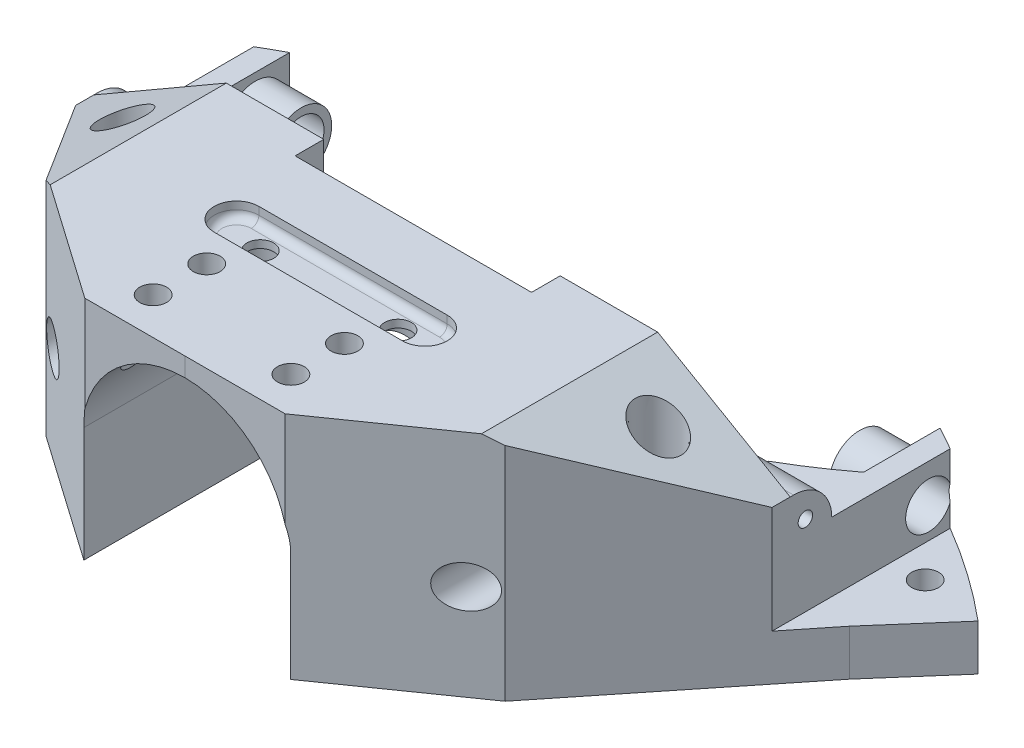
SolidWorks part; units mm, degrees
ref_plane "Front Plane" through (0, 0, 0) normal (0, 0, 1) x (1, 0, 0)
ref_plane "Top Plane" through (0, 0, 0) normal (0, 1, 0) x (1, 0, 0)
ref_plane "Right Plane" through (0, 0, 0) normal (1, 0, 0) x (0, 0, -1)
sketch "Sketch1" plane through (0, 0, 0) normal (0, 1, 0) x (1, 0, 0)
  circle A0 centre (0, 0) radius 90
extrude "Boss-Extrude1" add sketch "Sketch1" along normal blind 30
sketch "Sketch4" plane through (0, 30, 0) normal (0, 1, 0) x (1, 0, 0)
  line L0 (0, 90) -> (0, 55) construction
  line L1 (-42.5, 79.3332) -> (-42.5, 69.3332)
  line L2 (42.5, 79.3332) -> (42.5, 69.3332)
  line L3 (-42.5, 79.3332) -> (-42.5, 105.8098)
  line L4 (-42.5, 105.8098) -> (42.5, 105.8098)
  line L5 (42.5, 105.8098) -> (42.5, 79.3332)
  circle A0 centre (0, 0) radius 90 construction
  arc A1 (-42.5, 69.3332) -> (42.5, 69.3332) centre (0, 125.1761) ccw
  circle A5 centre (0, 0) radius 90 construction
  dimension "D1" = 35
  dimension "D2" = 42.5
  dimension "D3" = 42.5
  dimension "D4" = 10
  dimension "D5" = 10
extrude "Cut-Extrude2" cut sketch "Sketch4" against normal through all
sketch "Sketch9" plane through (0, 30, 0) normal (0, 1, 0) x (1, 0, 0)
  circle A0 centre (-49.7064, 70.1803) radius 1.75
  arc A1 (-42.5, 79.3332) -> (42.5, 79.3332) centre (0, 0) ccw construction
  dimension "D2" = 3.5
  dimension "D1" = 86
extrude "Cut-Extrude7" cut sketch "Sketch9" against normal through all
mirror "Mirror1" about plane through (0, 0, 0) normal (1, 0, 0) of "Cut-Extrude7"
sketch "Sketch10" plane through (0, 0, 0) normal (0, -1, 0) x (1, 0, 0)
  line L0 (57.8174, -68.9721) -> (50, -60)
  line L1 (50, -60) -> (30, -35)
  line L2 (-30, -35) -> (30, -35) construction
  line L3 (-30, -35) -> (-50, -60)
  line L4 (-50, -60) -> (-57.8174, -68.9721)
  line L5 (0, 0) -> (0, -35) construction
  line L6 (-30, -35) -> (-13.0885, -23.1584)
  line L7 (-13.0885, -23.1584) -> (0, -23.1584)
  line L8 (0, -23.1584) -> (13.0885, -23.1584)
  line L9 (13.0885, -23.1584) -> (30, -35)
  arc A0 (42.5, -79.3332) -> (-42.5, -79.3332) centre (0, 0) ccw construction
  point P14 (0, 0)
  dimension "D1" = 35
  dimension "D2" = 30
  dimension "D3" = 30
  dimension "D4" = 35
  dimension "D5" = 25
  dimension "D6" = 35
  dimension "D7" = 25
  dimension "D8" = 11.9
  dimension "D9" = 11.9
extrude "Cut-Extrude8" cut sketch "Sketch10" along direction (0, 1, 0) on the side against the normal through all and the other way through all flip side to cut
sketch "Sketch11" plane through (0, 0, -23.1584) normal (0, 0, 1) x (1, 0, 0)
  line L2 (-13.5, 15) -> (-13.5, 0)
  line L3 (-13.5, 0) -> (13.5, 0)
  line L4 (13.5, 15) -> (13.5, 0)
  arc A0 (13.5, 15) -> (-13.5, 15) centre (0, 14) ccw
  dimension "D2" = 27
  dimension "D3" = 15
  dimension "D5" = 15
sketch "Sketch13" plane through (42.5, 0, 0) normal (-1, 0, 0) x (0, 0, 1)
  line L0 (-79.3332, 0) -> (-79.3332, 30) construction
  line L1 (-69.3332, 0) -> (-79.3332, 0) construction
  circle A0 centre (-74.8332, 10) radius 4
  circle A1 centre (-74.8332, 10) radius 3
  dimension "D3" = 8
  dimension "D4" = 6
  dimension "D1" = 4.5
  dimension "D2" = 10
extrude "Boss-Extrude2" add sketch "Sketch13" along normal blind 6
sketch "Sketch14" plane through (0, 30, 0) normal (0, 1, 0) x (1, 0, 0)
  line L0 (-45.5, 77.6515) -> (-45.5, 54.375)
  line L1 (-30, 35) -> (-50, 60) construction
  line L2 (-42.5, 79.3332) -> (-42.5, 69.3332) construction
  arc A0 (-42.5, 79.3332) -> (-57.8174, 68.9721) centre (0, 0) ccw construction
  dimension "D1" = 3
extrude "Cut-Extrude11" cut sketch "Sketch14" against normal blind 24 and the other way through all flip side to cut
sketch "Sketch15" plane through (42.5, 0, 0) normal (-1, 0, 0) x (0, 0, 1)
  circle A0 centre (-74.8332, 10) radius 3
extrude "Cut-Extrude12" cut sketch "Sketch15" against normal through all
mirror "Mirror2" about plane through (0, 0, 0) normal (1, 0, 0) of "Cut-Extrude12", "Boss-Extrude2", "Cut-Extrude11"
other "Move Face1" parameters "D1"=0
ref_plane "Plane1" through (0, 0, -53) normal (0, 0, 1) x (1, 0, 0)
sketch "Sketch16" plane through (0, 0, -53) normal (0, 0, 1) x (1, 0, 0)
  line L1 (33, 19.5) -> (-33, 19.5)
  line L2 (35, 17.5) -> (35, 7.5)
  line L3 (33, 5.5) -> (-33, 5.5)
  line L4 (-35, 17.5) -> (-35, 7.5)
  line L5 (35, 19.5) -> (-35, 5.5) construction
  line L6 (35, 5.5) -> (-35, 19.5) construction
  arc A0 (-33, 19.5) -> (-35, 17.5) centre (-33, 17.5) ccw
  arc A1 (-33, 5.5) -> (-35, 7.5) centre (-33, 7.5) cw
  arc A2 (35, 7.5) -> (33, 5.5) centre (33, 7.5) cw
  arc A3 (33, 19.5) -> (35, 17.5) centre (33, 17.5) cw
  point P0 (0, 12.5)
  dimension "D3" = 2
  dimension "D1" = 5.5
  dimension "D2" = 14
  dimension "D4" = 70
  dimension "D5" = 35
extrude "Cut-Extrude13" cut sketch "Sketch16" against normal through all
sketch "Sketch17" plane through (0, 0, -53) normal (0, 0, -1) x (-1, 0, 0)
  circle A0 centre (-27, 12.5) radius 2.7228
  dimension "D1" = 12.5
  dimension "D2" = 27
extrude "Cut-Extrude14" cut sketch "Sketch17" against normal through all
mirror "Mirror3" about plane through (0, 0, 0) normal (1, 0, 0) of "Cut-Extrude14"
sketch "Sketch20" plane through (0, 30, 0) normal (0, 1, 0) x (1, 0, 0)
  line L1 (-63.9229, 90.6989) -> (72.019, 90.6989)
  line L2 (-63.9229, 90.6989) -> (-63.9229, 56.7436)
  line L3 (-63.9229, 56.7436) -> (72.019, 56.7436)
  line L4 (72.019, 90.6989) -> (72.019, 56.7436)
extrude "Cut-Extrude16" cut sketch "Sketch20" against normal blind 10
ref_plane "Plane3" through (0, 27, 0) normal (0, 1, 0) x (1, 0, 0)
sketch "Sketch21" plane through (0, 27, 0) normal (0, 1, 0) x (1, 0, 0)
  line L0 (-9, 42) -> (9, 42) construction
  line L2 (13.0885, 23.1584) -> (0, 23.1584) construction
  line L3 (0, 42) -> (0, 23.1584) construction
  circle A0 centre (-9, 42) radius 3
  circle A1 centre (9, 42) radius 3
  dimension "D4" = 6
  dimension "D5" = 6
  dimension "D1" = 18.8416
  dimension "D2" = 18
extrude "Cut-Extrude17" cut sketch "Sketch21" against normal through all
sketch "Sketch22" plane through (0, 27, 0) normal (0, -1, 0) x (1, 0, 0)
  circle A0 centre (-9, -42) radius 1.75
  circle A1 centre (9, -42) radius 1.75
  dimension "D1" = 3.5
  dimension "D2" = 3.5
extrude "Cut-Extrude18" cut sketch "Sketch22" against normal through all
sketch "Sketch23" plane through (0, 20, 0) normal (0, 1, 0) x (1, 0, 0)
  line L1 (-63.9229, 86.5905) -> (64.5271, 86.5905)
  line L2 (-63.9229, 86.5905) -> (-63.9229, 62.1813)
  line L3 (-63.9229, 62.1813) -> (64.5271, 62.1813)
  line L4 (64.5271, 86.5905) -> (64.5271, 62.1813)
extrude "Cut-Extrude19" cut sketch "Sketch23" against normal blind 5
fillet "Fillet3" radius 5 2 edges at (-38.2124, 20, -62.1813) (38.2124, 20, -62.1813)
extrude "Cut-Extrude20" cut sketch "Sketch11" against normal through all
sketch "Sketch24" plane through (0, 30, 0) normal (0, 1, 0) x (1, 0, 0)
  line L1 (-14, -71.7161) -> (14, -71.7161)
  line L2 (-14, -71.7161) -> (-14, 71.7161)
  line L3 (-14, 71.7161) -> (14, 71.7161)
  line L4 (14, -71.7161) -> (14, 71.7161)
  line L5 (-14, -71.7161) -> (14, 71.7161) construction
  line L6 (-14, 71.7161) -> (14, -71.7161) construction
  point P0 (0, 0)
  dimension "D1" = 28
pattern_linear "LPattern1" count 3 spacing 7 along (0, 0, 1) of "Cut-Extrude17", "Cut-Extrude18"
sketch "Sketch25" plane through (-45.5, 0, 0) normal (-1, 0, 0) x (0, 0, 1)
  circle A0 centre (-58.7334, 16.5025) radius 0.9425
  point P2 (-58.7334, 16.5025)
extrude "Cut-Extrude22" cut sketch "Sketch25" against normal through all
sketch "Sketch26" plane through (0, 30, 0) normal (0, 1, 0) x (1, 0, 0)
  line L0 (-12.102, 42) -> (12.5104, 42) construction
  line L1 (-12.102, 44.9197) -> (12.5104, 44.9197)
  line L2 (-12.102, 39.0803) -> (12.5104, 39.0803)
  arc A1 (-12.102, 44.9197) -> (-12.102, 39.0803) centre (-12.102, 42) ccw
  arc A2 (12.5104, 39.0803) -> (12.5104, 44.9197) centre (12.5104, 42) ccw
  circle A4 centre (-9, 28) radius 1.75 construction
  point P1 (0.2042, 42)
  point P9 (12.5104, 41.6361)
  dimension "D1" = 14
extrude "Cut-Extrude23" cut sketch "Sketch26" against normal blind 2
fillet "Fillet4" radius 1 4 edges at (15.4301, 28, -42) (0.2042, 28, -39.0803) (-15.0217, 28, -42) (0.2042, 28, -44.9197)
sketch "Sketch28" plane through (0, 0, -53) normal (0, 0, 1) x (1, 0, 0)
  line L1 (-15.4469, -40.4936) -> (15.4469, -40.4936)
  line L2 (-15.4469, -40.4936) -> (-15.4469, 40.4936)
  line L3 (-15.4469, 40.4936) -> (15.4469, 40.4936)
  line L4 (15.4469, -40.4936) -> (15.4469, 40.4936)
  line L5 (-15.4469, -40.4936) -> (15.4469, 40.4936) construction
  line L6 (-15.4469, 40.4936) -> (15.4469, -40.4936) construction
  point P0 (0, 0)
extrude "Cut-Extrude24" cut sketch "Sketch28" against normal through all
sketch "Sketch29" plane through (0, 30, 0) normal (0, 1, 0) x (1, 0, 0)
  line L0 (-35, 50) -> (35, 50) construction
  line L1 (0, 50) -> (0, 0) construction
  circle A0 centre (-35, 50) radius 3
  circle A1 centre (35, 50) radius 3
  dimension "D3" = 6
  dimension "D4" = 6
  dimension "D1" = 70
  dimension "D2" = 50
chamfer "Chamfer3" distance 10 angle 60 1 edges at (45.5, 30, -55.5593) first distance on face at (45.5, 16.5025, -59.676)
chamfer "Chamfer2" distance 10 angle 60 1 edges at (-45.5, 30, -55.5593) first distance on face at (-45.5, 16.5025, -57.7909)
extrude "Cut-Extrude37" cut sketch "Sketch29" against normal blind 25 draft 0.1
sketch "Sketch30" plane through (0, 5, 0) normal (0, 1, 0) x (1, 0, 0)
  circle A0 centre (-35, 50) radius 1.75
  circle A1 centre (35, 50) radius 1.75
  dimension "D1" = 3.5
  dimension "D2" = 3.5
extrude "Cut-Extrude38" cut sketch "Sketch30" against normal through all
